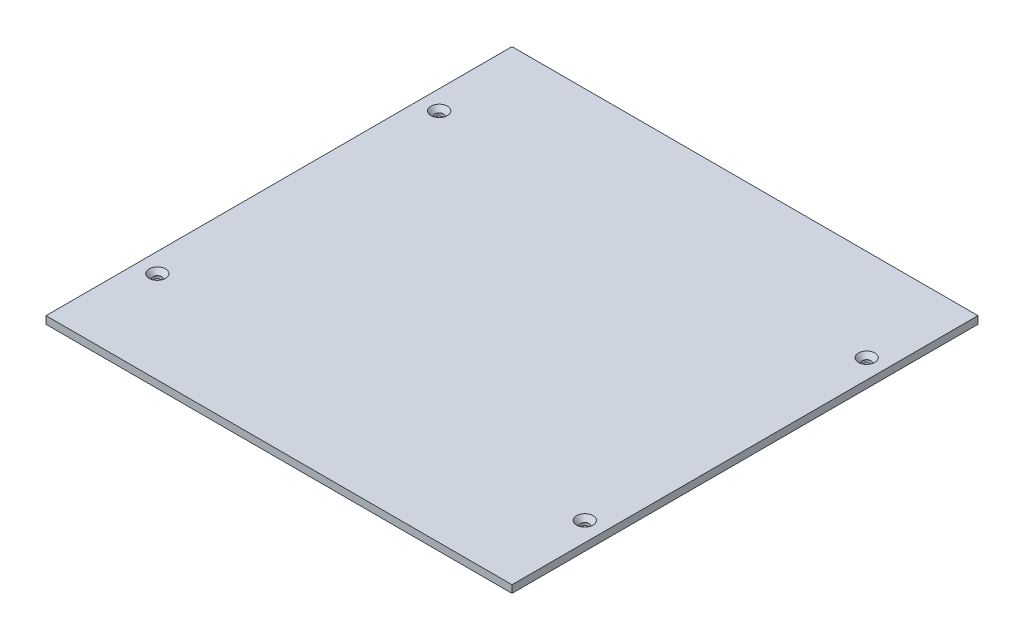
SolidWorks part; units mm, degrees
material "6061-T4 (SS)"
ref_plane "Front Plane" through (0, 0, 0) normal (0, 0, 1) x (1, 0, 0)
ref_plane "Top Plane" through (0, 0, 0) normal (0, 1, 0) x (1, 0, 0)
ref_plane "Right Plane" through (0, 0, 0) normal (1, 0, 0) x (0, 0, -1)
sketch "Sketch1" plane through (0, 0, 0) normal (0, 1, 0) x (1, 0, 0)
  line L1 (0, 0) -> (99.2004, 0)
  line L2 (0, 0) -> (0, 99.2004)
  line L3 (0, 99.2004) -> (99.2004, 99.2004)
  line L4 (99.2004, 0) -> (99.2004, 99.2004)
  dimension "D1" = 99.2004
  dimension "D2" = 99.2004
extrude "Boss-Extrude1" add sketch "Sketch1" along normal blind 1.6002
sketch "Sketch3" plane through (0, 1.6002, 0) normal (0, 1, 0) x (1, 0, 0)
  line L0 (0, 0) -> (1.6002, 0) construction
  line L1 (0, 0) -> (99.2004, 0) construction
  line L2 (1.6002, 0) -> (1.6002, 99.2004) construction
  line L3 (99.2004, 99.2004) -> (0, 99.2004) construction
  line L4 (0, 97.6002) -> (1.6002, 97.6002) construction
  line L5 (0, 99.2004) -> (0, 0) construction
  line L6 (1.6002, 97.6002) -> (97.6002, 97.6002) construction
  line L7 (97.6002, 97.6002) -> (97.6002, 99.2004) construction
  line L8 (97.6002, 97.6002) -> (97.6002, 0) construction
  line L9 (99.2004, 0) -> (99.2004, 99.2004) construction
  line L10 (49.6002, 97.6002) -> (49.6002, 49.6002) construction
  line L11 (95.1002, 49.6002) -> (4.1002, 49.6002) construction
  line L12 (4.1002, 49.6002) -> (4.1002, 79.6002) construction
  line L13 (4.1002, 49.6002) -> (4.1002, 19.6002) construction
  line L14 (95.1002, 49.6002) -> (95.1002, 19.6002) construction
  line L15 (95.1002, 49.6002) -> (95.1002, 79.6002) construction
  line L16 (1.6002, 1.6002) -> (97.6002, 1.6002) construction
  line L17 (49.6002, 49.6002) -> (49.6002, 1.6002) construction
  dimension "D1" = 1.6002
  dimension "D2" = 1.6002
  dimension "D3" = 1.6002
  dimension "D4" = 2.5
  dimension "D5" = 30
  dimension "D6" = 1.6002
hole_wizard "CSK for #0 Flat Head Socket Cap Screw1" positions "Sketch4" profile "Sketch5" countersink size "#0" standard "ANSI Inch" end condition through all
sketch "Sketch4" plane through (0, 1.6002, 0) normal (0, 1, 0) x (1, 0, 0)
  point P0 (4.1002, 79.6002)
  point P3 (4.1002, 19.6002)
  point P6 (95.1002, 19.6002)
  point P9 (95.1002, 79.6002)
sketch "Sketch5" plane through (4.1002, 1.6002, -79.6002) normal (1, 0, 0) x (0, 0, 1)
  line L0 (0, 0) -> (0, 1.6002)
  line L1 (0, 1.6002) -> (0.889, 1.6002)
  line L2 (0.889, 1.6002) -> (0.889, 0.9935)
  line L3 (0.889, 0.9935) -> (1.7526, 0)
  line L5 (1.7526, 0) -> (0, 0)
  line L6 (-0.889, 0.9935) -> (-1.7526, 0) construction
  line L11 (0, -6.35) -> (0, 107.95) construction
  dimension "Thru Hole Dia." = 1.778
  dimension "Thru Hole Depth" = 1.6002
  dimension "Near C'Sink Dia." = 3.5052
  dimension "Near C'Sink Angle" = 82
sketch "Sketch7" [suppressed] plane through (0, 1.6002, 0) normal (0, 1, 0) x (1, 0, 0)
  circle A0 centre (6.7377, 9.5952) radius 1.6
  circle A1 centre (6.7377, 89.6052) radius 1.6
  circle A2 centre (92.4627, 85.7952) radius 1.6
  circle A3 centre (92.4627, 12.1352) radius 1.6
  circle A4 centre (92.4627, 12.1352) radius 1.6 construction
  circle A5 centre (6.7377, 9.5952) radius 1.6 construction
  circle A6 centre (6.7377, 89.6052) radius 1.6 construction
  circle A7 centre (92.4627, 85.7952) radius 1.6 construction
extrude "Cut-Extrude1" [suppressed] cut sketch "Sketch7" against normal blind 10
sketch "Sketch8" [suppressed] plane through (0, 1.6002, 0) normal (0, 1, 0) x (1, 0, 0)
  circle A0 centre (92.4627, 9.5952) radius 1.6
  circle A1 centre (92.4627, 89.6052) radius 1.6
  circle A2 centre (6.7377, 85.7952) radius 1.6
  circle A3 centre (6.7377, 12.1352) radius 1.6
  circle A4 centre (6.7377, 12.1352) radius 1.6 construction
  circle A5 centre (92.4627, 9.5952) radius 1.6 construction
  circle A6 centre (92.4627, 89.6052) radius 1.6 construction
  circle A7 centre (6.7377, 85.7952) radius 1.6 construction
extrude "Cut-Extrude2" [suppressed] cut sketch "Sketch8" against normal blind 10
